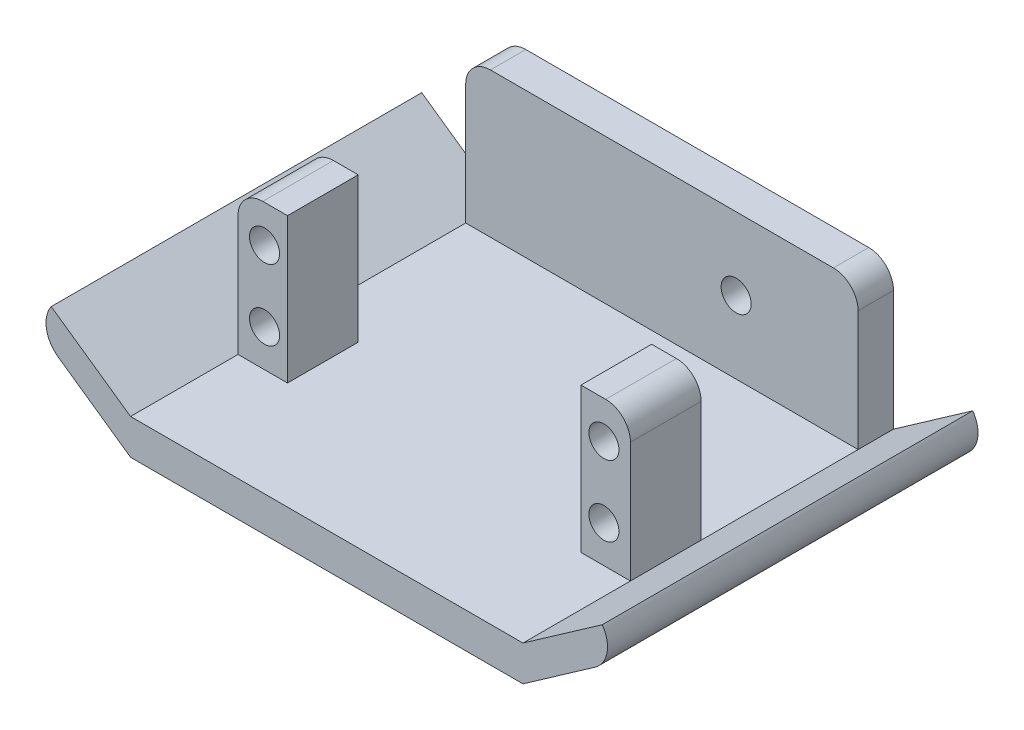
SolidWorks part; units mm, degrees
ref_plane "Front" through (0, 0, 0) normal (0, 0, 1) x (1, 0, 0)
ref_plane "Top" through (0, 0, 0) normal (0, 1, 0) x (1, 0, 0)
ref_plane "Right" through (0, 0, 0) normal (1, 0, 0) x (0, 0, -1)
sketch "Sketch1" plane through (0, 0, 0) normal (0, 1, 0) x (1, 0, 0)
  line L1 (0, 0) -> (55.5, 0)
  line L2 (0, 0) -> (0, 40.4)
  line L3 (0, 40.4) -> (55.5, 40.4)
  line L4 (55.5, 0) -> (55.5, 40.4)
  dimension "D1" = 55.5
  dimension "D2" = 40.4
extrude "base" add sketch "Sketch1" along normal blind 5
sketch "Sketch2" plane through (0, 0, -40.4) normal (0, 0, -1) x (-1, 0, 0)
  line L1 (0, 5) -> (0, 0) construction
  line L2 (-55.5, 0) -> (0, 0)
  line L3 (-55.5, 0) -> (-55.5, 25.5)
  line L4 (-55.5, 25.5) -> (0, 25.5)
  line L5 (0, 0) -> (0, 25.5)
  line L6 (-55.5, 5) -> (0, 5) construction
  dimension "D1" = 20.5
extrude "wall" add sketch "Sketch2" against normal blind 5
ref_plane "Plane1" through (0, 0, -8.2) normal (0, 0, 1) x (1, 0, 0)
sketch "Sketch3" plane through (0, 0, -8.2) normal (0, 0, 1) x (1, 0, 0)
  line L0 (0, 5) -> (55.5, 5) construction
  line L1 (0, 25.5) -> (7, 25.5)
  line L2 (0, 25.5) -> (0, 5)
  line L3 (0, 5) -> (7, 5)
  line L4 (7, 25.5) -> (7, 5)
  line L5 (27.75, 5) -> (27.75, 25.5) construction
  line L6 (55.5, 5) -> (0, 5) construction
  line L7 (0, 25.5) -> (55.5, 25.5) construction
  line L8 (55.5, 5) -> (48.5, 5)
  line L9 (48.5, 25.5) -> (48.5, 5)
  line L10 (55.5, 25.5) -> (48.5, 25.5)
  line L11 (55.5, 25.5) -> (55.5, 5)
  dimension "D1" = 7
extrude "mountingTabs" add sketch "Sketch3" along normal blind 5
sketch "Sketch4" plane through (0, 0, 0) normal (0, 0, 1) x (1, 0, 0)
  line L0 (27.75, 0) -> (27.75, 25.5) construction
  line L1 (0, 0) -> (55.5, 0) construction
  line L2 (0, 25.5) -> (55.5, 25.5) construction
  line L3 (0, 0) -> (-10.2089, 7.1483)
  line L4 (0, 5) -> (-11.2182, 12.8551)
  line L5 (0, 5) -> (0, 0)
  line L6 (55.5, 5) -> (66.7182, 12.8551)
  line L7 (55.5, 5) -> (55.5, 0)
  line L8 (55.5, 0) -> (65.7089, 7.1483)
  arc A0 (-11.2182, 12.8551) -> (-10.2089, 7.1483) centre (-7.8572, 10.5069) ccw
  arc A1 (66.7182, 12.8551) -> (65.7089, 7.1483) centre (63.3572, 10.5069) cw
  dimension "D1" = 145
  dimension "D2" = 12.4627
  dimension "D3" = 13.6949
extrude "lips" add sketch "Sketch4" against normal up to surface (40.4 mm away) up to face at (27.75, 12.75, -40.4)
sketch "Sketch5" plane through (0, 0, -3.2) normal (0, 0, 1) x (1, 0, 0)
  line L0 (27.75, 0) -> (27.75, 25.5) construction
  line L3 (0, 15.25) -> (55.5, 15.25) construction
  line L4 (0, 25.5) -> (0, 5) construction
  line L5 (55.5, 5) -> (55.5, 25.5) construction
  line L6 (7, 25.5) -> (0, 25.5) construction
  line L7 (0, 0) -> (55.5, 0) construction
  line L8 (0, 25.5) -> (55.5, 25.5) construction
  circle A0 centre (3.75, 20.25) radius 2.125
  circle A1 centre (3.75, 10.25) radius 2.125
  circle A4 centre (51.75, 10.25) radius 2.125
  circle A5 centre (51.75, 20.25) radius 2.125
  dimension "D1" = 4.25
  dimension "D2" = 5.25
  dimension "D3" = 3.75
extrude "mountingHoles" cut sketch "Sketch5" against normal blind 5
fillet "fillets" radius 3.5 4 edges at (55.5, 25.5, -37.9) (55.5, 25.5, -5.7) (0, 25.5, -37.9) (0, 25.5, -5.7)
sketch "Sketch6" plane through (0, 0, -35.4) normal (0, 0, 1) x (1, 0, 0)
  line L0 (3.5, 25.5) -> (52, 25.5) construction
  line L1 (55.5, 5) -> (55.5, 22) construction
  circle A0 centre (38.25, 15.25) radius 2.125
  dimension "D1" = 4.25
  dimension "D2" = 10.25
  dimension "D3" = 17.25
extrude "throughHole" cut sketch "Sketch6" against normal blind 5
sketch "Sketch7" plane through (0, 0, -8.2) normal (0, 0, -1) x (-1, 0, 0)
  line L4 (-48.5, 25.5) -> (-52, 25.5)
  line L5 (-55.5, 22) -> (-55.5, 5)
  line L6 (-55.5, 5) -> (-48.5, 5)
  line L7 (-48.5, 5) -> (-48.5, 25.5)
  line L8 (-48.5, 25.5) -> (-52, 25.5)
  line L9 (-55.5, 22) -> (-55.5, 5)
  line L10 (-55.5, 5) -> (-48.5, 5)
  line L11 (-48.5, 5) -> (-48.5, 25.5)
  line L12 (0, 5) -> (0, 22)
  line L13 (-3.5, 25.5) -> (-7, 25.5)
  line L14 (-7, 25.5) -> (-7, 5)
  line L15 (-7, 5) -> (0, 5)
  line L16 (0, 5) -> (0, 22)
  line L17 (-3.5, 25.5) -> (-7, 25.5)
  line L18 (-7, 25.5) -> (-7, 5)
  line L19 (-7, 5) -> (0, 5)
  circle A0 centre (-51.75, 20.25) radius 2.125 construction
  arc A1 (-52, 25.5) -> (-55.5, 22) centre (-52, 22) ccw
  arc A2 (-52, 25.5) -> (-55.5, 22) centre (-52, 22) ccw
  arc A3 (0, 22) -> (-3.5, 25.5) centre (-3.5, 22) ccw
  arc A4 (0, 22) -> (-3.5, 25.5) centre (-3.5, 22) ccw
  circle A5 centre (-51.75, 20.25) radius 2.125
  circle A6 centre (-51.75, 10.25) radius 2.125 construction
  circle A7 centre (-51.75, 10.25) radius 2.125
  circle A8 centre (-3.75, 10.25) radius 2.125 construction
  circle A9 centre (-3.75, 10.25) radius 2.125
  circle A10 centre (-3.75, 20.25) radius 2.125 construction
  circle A11 centre (-3.75, 20.25) radius 2.125
  dimension "D1" = 0
  dimension "D2" = 0
extrude "Boss-Extrude1" add sketch "Sketch7" along normal blind 5
sketch "Sketch8" plane through (0, 0, 0) normal (0, 0, 1) x (1, 0, 0)
  line L6 (0, 0) -> (55.5, 0)
  line L7 (55.5, 0) -> (65.7089, 7.1483)
  line L8 (66.7182, 12.8551) -> (55.5, 5)
  line L9 (55.5, 5) -> (0, 5)
  line L10 (0, 5) -> (-11.2182, 12.8551)
  line L11 (-10.2089, 7.1483) -> (0, 0)
  line L12 (0, 0) -> (55.5, 0)
  line L13 (55.5, 0) -> (65.7089, 7.1483)
  line L14 (66.7182, 12.8551) -> (55.5, 5)
  line L15 (55.5, 5) -> (0, 5)
  line L16 (0, 5) -> (-11.2182, 12.8551)
  line L17 (-10.2089, 7.1483) -> (0, 0)
  arc A2 (65.7089, 7.1483) -> (66.7182, 12.8551) centre (63.3572, 10.5069) ccw
  arc A3 (-11.2182, 12.8551) -> (-10.2089, 7.1483) centre (-7.8572, 10.5069) ccw
  arc A4 (65.7089, 7.1483) -> (66.7182, 12.8551) centre (63.3572, 10.5069) ccw
  arc A5 (-11.2182, 12.8551) -> (-10.2089, 7.1483) centre (-7.8572, 10.5069) ccw
  dimension "D1" = 0
extrude "Boss-Extrude2" add sketch "Sketch8" along normal blind 12
